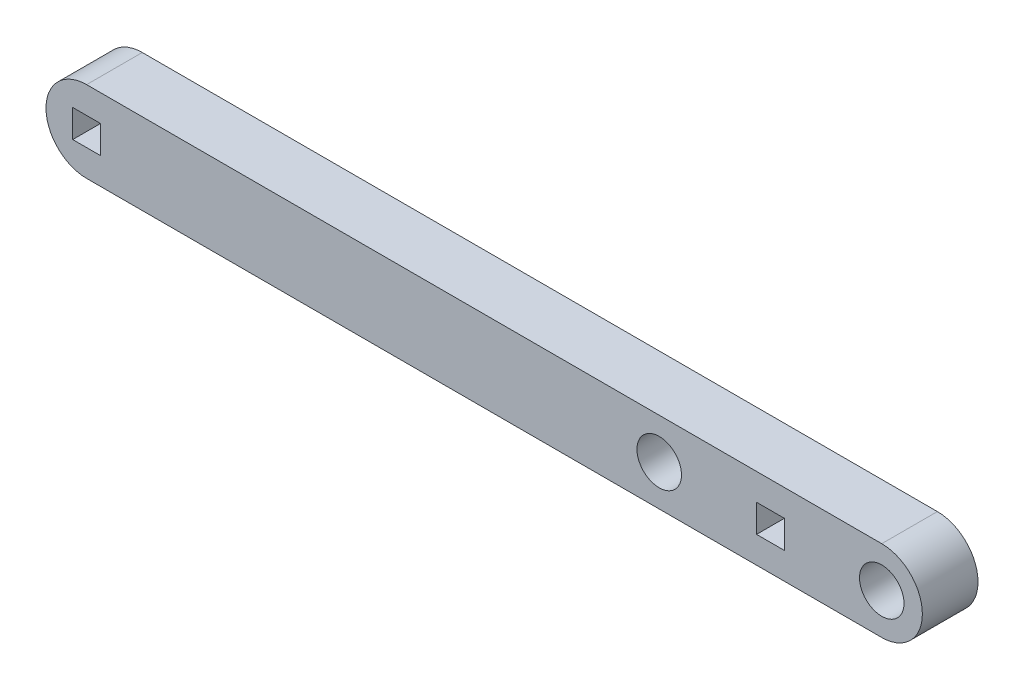
SolidWorks part; units mm, degrees
material "ABS"
ref_plane "Front Plane" through (0, 0, 0) normal (0, 0, 1) x (1, 0, 0)
ref_plane "Top Plane" through (0, 0, 0) normal (0, 1, 0) x (1, 0, 0)
ref_plane "Right Plane" through (0, 0, 0) normal (1, 0, 0) x (0, 0, -1)
sketch "Sketch1" plane through (0, 0, 0) normal (0, 0, 1) x (1, 0, 0)
  line L0 (0, 0) -> (90.7542, 0) construction
  line L1 (0, 4.6368) -> (90.7542, 4.6368)
  line L2 (0, -4.6368) -> (90.7542, -4.6368)
  line L3 (76.4667, -1.5875) -> (79.6417, -1.5875)
  line L4 (-1.5875, -1.5875) -> (1.5875, -1.5875)
  line L5 (-1.5875, -1.5875) -> (-1.5875, 1.5875)
  line L6 (-1.5875, 1.5875) -> (1.5875, 1.5875)
  line L7 (1.5875, -1.5875) -> (1.5875, 1.5875)
  line L8 (-1.5875, -1.5875) -> (1.5875, 1.5875) construction
  line L9 (-1.5875, 1.5875) -> (1.5875, -1.5875) construction
  line L10 (76.4667, -1.5875) -> (76.4667, 1.5875)
  line L11 (76.4667, 1.5875) -> (79.6417, 1.5875)
  line L12 (79.6417, -1.5875) -> (79.6417, 1.5875)
  line L13 (76.4667, 1.5875) -> (79.6417, -1.5875) construction
  line L14 (79.6417, 1.5875) -> (76.4667, -1.5875) construction
  arc A0 (0, 4.6368) -> (0, -4.6368) centre (0, 0) ccw
  arc A1 (90.7542, -4.6368) -> (90.7542, 4.6368) centre (90.7542, 0) ccw
  circle A2 centre (90.7542, 0) radius 2.54
  circle A4 centre (65.3542, 0) radius 2.54
  point P3 (45.3771, 0)
  point P8 (0, 0)
  point P17 (78.0542, 0)
  point P20 (0, 0)
  point P21 (0, 0)
  point P24 (0, 0)
  dimension "D4" = 5.08
  dimension "D5" = 12.7
  dimension "D1" = 90.7542
  dimension "D2" = 3.175
  dimension "D3" = 78.0542
extrude "Boss-Extrude1" add sketch "Sketch1" along normal blind 6.35
ref_plane "Plane1" through (39.0271, 39.0271, 0) normal (-0.7071, -0.7071, 0) x (-0.7071, 0.7071, 0)
ref_plane "Plane2" through (39.0271, -39.0271, 0) normal (-0.7071, 0.7071, 0) x (0, 0, -1)
ref_axis "Axis1" through (78.0542, 0, 6.6675) along (0, 0, -1)
